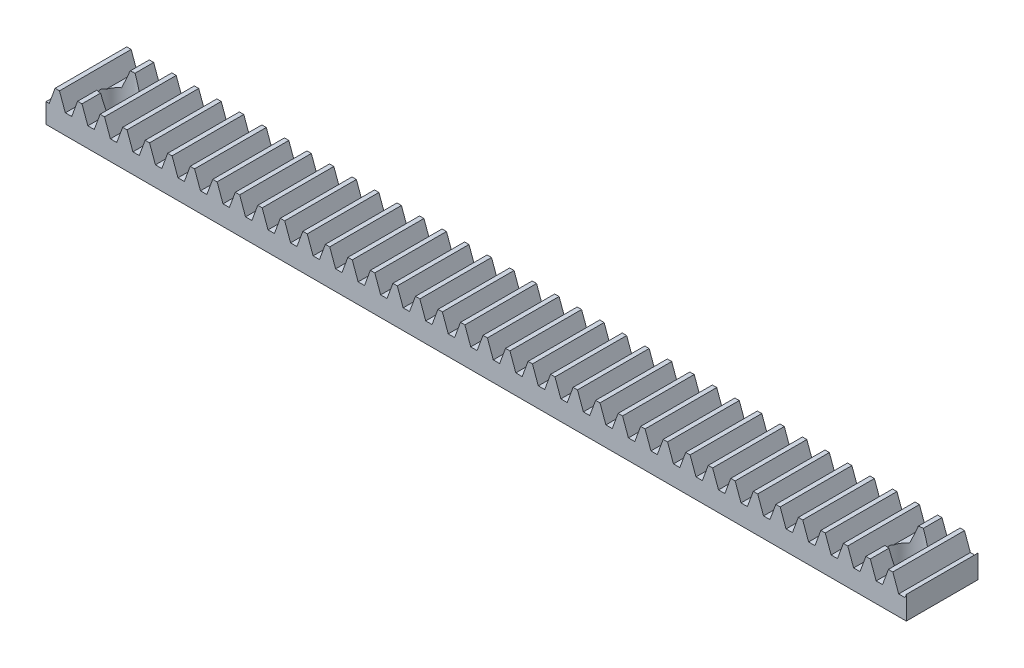
SolidWorks part; units mm, degrees
extrude "Blank" add sketch "BlankSke" against normal blind 5
sketch "BlankSke" plane through (0, 0, 0) normal (0, 0, 1) x (1, 0, 0)
  line L1 (0, 0) -> (60, 0)
  line L2 (0, 0) -> (0, 2.5)
  line L3 (0, 2.5) -> (60, 2.5)
  line L4 (60, 0) -> (60, 2.5)
  dimension "Length" = 60
ref_plane "Plane1" through (0, 0, 0) normal (0, 0, 1) x (1, 0, 0)
ref_plane "Plane2" through (0, 0, 0) normal (0, 1, 0) x (1, 0, 0)
ref_plane "Plane3" through (0, 0, 0) normal (1, 0, 0) x (0, 0, -1)
other "Configuration Table"
sketch "HoldingSke" plane through (0, 0, 0) normal (0, 1, 0) x (1, 0, 0)
  line L0 (0, 0) -> (0.2783, 1.9805)
  line L1 (-15, 0) -> (100, 0) construction
  line L2 (0, 0) -> (-2.1039, 2.3779)
  line L3 (0, 0) -> (-11.863, 4.5341)
  line L4 (0, 0) -> (6.6156, 5.5511)
  line L5 (0, 0) -> (-23.7986, -8.8762)
  line L6 (0, 0) -> (-10.5278, -7.1032)
  line L9 (-71.009, 38.7566) -> (-14.6274, 59.2778)
  line L10 (-76.2, 2.8779) -> (-74.2, 2.8779)
  line L11 (0, 0) -> (-5, 0)
  line L12 (-76.2, 101.6) -> (-76.181, 101.6)
  line L13 (24.9733, 27.94) -> (52.9518, 28.4284)
  line L14 (24.9733, 27.94) -> (24.9743, 27.94)
  line L15 (24.9733, 27.94) -> (100.4006, 29.5858)
  circle A0 centre (0, 0) radius 19.05
  circle A1 centre (0, 0) radius 1
  circle A2 centre (0, 0) radius 12.7
  dimension "Num_teeth" = 40
  dimension "Width" = 5
  dimension "Length" = 60
  dimension "Pitch_height" = 2
sketch "TooCutSkeIll" plane through (0, 0, 0) normal (0, 0, 1) x (1, 0, 0)
  line L0 (-0.6269, 2.4868) -> (-0.2524, 1.4579)
  line L1 (-0.134, 1.375) -> (0.134, 1.375)
  line L2 (0.2524, 1.4579) -> (0.6269, 2.4868)
  line L3 (60, 2.5) -> (0, 2.5) construction
  line L4 (0, 0) -> (0, 64.897) construction
  line L5 (-13.208, 2) -> (12.954, 2) construction
  line L6 (0, 0) -> (60, 0) construction
  line L7 (0.4497, 2) -> (0.4497, 48.7463) construction
  line L8 (-0.4497, 2) -> (-0.4497, 48.7463) construction
  line L9 (0.6457, 2.5) -> (0.6457, 2.5254)
  line L10 (-0.6457, 2.5) -> (-0.6457, 2.5254)
  line L11 (-0.6457, 2.5254) -> (0.6457, 2.5254)
  arc A0 (0.134, 1.375) -> (0.2524, 1.4579) centre (0.134, 1.501) ccw
  arc A1 (-0.2524, 1.4579) -> (-0.134, 1.375) centre (-0.134, 1.501) ccw
  arc A2 (0.6457, 2.5) -> (0.6269, 2.4868) centre (0.6457, 2.48) ccw
  arc A3 (-0.6269, 2.4868) -> (-0.6457, 2.5) centre (-0.6457, 2.48) ccw
  dimension "Addendum_plus" = 0.5254
  dimension "Pitch_height" = 2
  dimension "Pressure_angle" = 20
  dimension "Gap_width" = 0.8994
  dimension "Dedendum" = 0.625
extrude "ToothCutIll" [suppressed] cut sketch "TooCutSkeIll" against normal through all
sketch "TooCutSkeSim" plane through (0, 0, 0) normal (0, 0, 1) x (1, 0, 0)
  line L0 (0.2222, 1.375) -> (-0.2222, 1.375)
  line L1 (0.6409, 2.5254) -> (0.2222, 1.375)
  line L2 (0, 17.4625) -> (0, 53.467) construction
  line L3 (0.6409, 2.5254) -> (-0.6409, 2.5254)
  line L6 (-0.6409, 2.5254) -> (-0.2222, 1.375)
  line L9 (-0.4497, 2) -> (0.4497, 2) construction
  line L10 (0, 0) -> (60, 0) construction
  line L11 (0.4497, 2) -> (0.4497, 53.467) construction
  line L12 (-0.4497, 2) -> (-0.4497, 53.467) construction
  dimension "Addendum_plus" = 0.5254
  dimension "Pitch_height" = 2
  dimension "Pressure_angle" = 20
  dimension "Gap_width" = 0.8994
  dimension "Dedendum" = 0.625
extrude "ToothCutSim" cut sketch "TooCutSkeSim" against normal through all
pattern_linear "TeethCuts" count 40 spacing 1.5708 along (1, 0, 0) of "ToothCutIll", "ToothCutSim"
sketch "Sketch1" plane through (0, 0, 0) normal (0, -1, 0) x (1, 0, 0)
  circle A0 centre (2.5, -2.5) radius 1.2
  circle A1 centre (57.5, -2.5) radius 1.2
extrude "Cut-Extrude1" cut sketch "Sketch1" against normal blind 10
equation "' \"Module@HoldingSke\" = 6.35"
equation "' \"Num_teeth@HoldingSke\" = 12"
equation "' \"Ap@HoldingSke\" =  20"
equation "' \"Ap@HoldingSke\" = 20"
equation "' \"Width@HoldingSke\" = 0.25 * 25.4"
equation "' \"Show_teeth@HoldingSke\" = 500"
equation "' \"Backlash@HoldingSke\" = 0.009 * 25.4"
equation "' \"Addendum_fac@HoldingSke\" = 1.0"
equation "' \"Dedendum_fac@HoldingSke\" = 1.25"
equation "' \"Dedendum_add@HoldingSke\" = 0.00005 * 25.4"
equation "' \"Clearance_fac@HoldingSke\" = 0.25"
equation "' \"Pitch_height@HoldingSke\" = 1 * 25.4"
equation "' \"Length@HoldingSke\" = 4.71 * 25.4"
equation "\"Pitch@HoldingSke\" = 1 / \"Module@HoldingSke\""
equation "\"MPH@HoldingSke\" = \"Dedendum_fac@HoldingSke\" / \"Pitch@HoldingSke\" + 2 * \"Dedendum_add@HoldingSke\" + 0.002 * 25.4"
equation "\"MPH@HoldingSke\" = ((sgn( \"MPH@HoldingSke\" - \"Pitch_height@HoldingSke\")+1)*( \"MPH@HoldingSke\" - \"Pitch_height@HoldingSke\"))/2 + \"Pitch_height@HoldingSke\""
equation "\"Blank_height@BlankSke\" = \"Pitch_height@HoldingSke\" + \"Addendum_fac@HoldingSke\"  / \"Pitch@HoldingSke\" "
equation "\"Length@BlankSke\" =  \"Length@HoldingSke\""
equation "\"Face_width@Blank\" = \"Width@HoldingSke\""
equation "\"Pressure_angle@TooCutSkeIll\" = \"Ap@HoldingSke\""
equation "\"Addendum_plus@TooCutSkeIll\" =  \"Addendum_fac@HoldingSke\"  / \"Pitch@HoldingSke\" + 0.001 *25.4"
equation "\"Dedendum@TooCutSkeIll\" = \"Dedendum_fac@HoldingSke\"  / \"Pitch@HoldingSke\""
equation "\"Pitch_height@TooCutSkeIll\" =  \"MPH@HoldingSke\""
equation "\"Gap_width@TooCutSkeIll\" = 3.14159265 / 2 / \"Pitch@HoldingSke\" + 6 * \"Backlash@HoldingSke\""
equation "\"Pressure_angle@TooCutSkeSim\" = \"Ap@HoldingSke\""
equation "\"Addendum_plus@TooCutSkeSim\" =  \"Addendum_fac@HoldingSke\"  / \"Pitch@HoldingSke\" + 0.001 * 25.4"
equation "\"Dedendum@TooCutSkeSim\" = \"Dedendum_fac@HoldingSke\"  / \"Pitch@HoldingSke\""
equation "\"Pitch_height@TooCutSkeSim\" =  \"MPH@HoldingSke\""
equation "\"Gap_width@TooCutSkeSim\" = 3.14159265 / 2 / \"Pitch@HoldingSke\" + 6 * \"Backlash@HoldingSke\""
equation "\"Root_fillet@TooCutSkeIll\" = \"Clearance_fac@HoldingSke\" / \"Pitch@HoldingSke\" + \"Dedendum_add@HoldingSke\""
equation "\"Break_rad@TooCutSkeIll\" = 0.02 / \"Pitch@HoldingSke\" * 2"
equation "\"Linear_pitch@TeethCuts\" = 3.14159265 / \"Pitch@HoldingSke\""
equation "\"Num_teeth@HoldingSke\" = int( ( \"Length@HoldingSke\" + 0 ) / (3.14159265 / \"Pitch@HoldingSke\")) + 0.9999  + 1"
equation " \"Num_teeth@TeethCuts\" = int( \"Show_teeth@HoldingSke\" ) + 1"
equation " \"Num_teeth@TeethCuts\" = ((sgn( \"Num_teeth@TeethCuts\" - \"Num_teeth@HoldingSke\" )-1)*( \"Num_teeth@TeethCuts\" - \"Num_teeth@HoldingSke\" ))/-2+ \"Num_teeth@HoldingSke\""
equation " \"Num_teeth@TeethCuts\" = ((sgn( \"Num_teeth@TeethCuts\" - 2.0)+1)*( \"Num_teeth@TeethCuts\" - 2.0))/2 +2.0"
